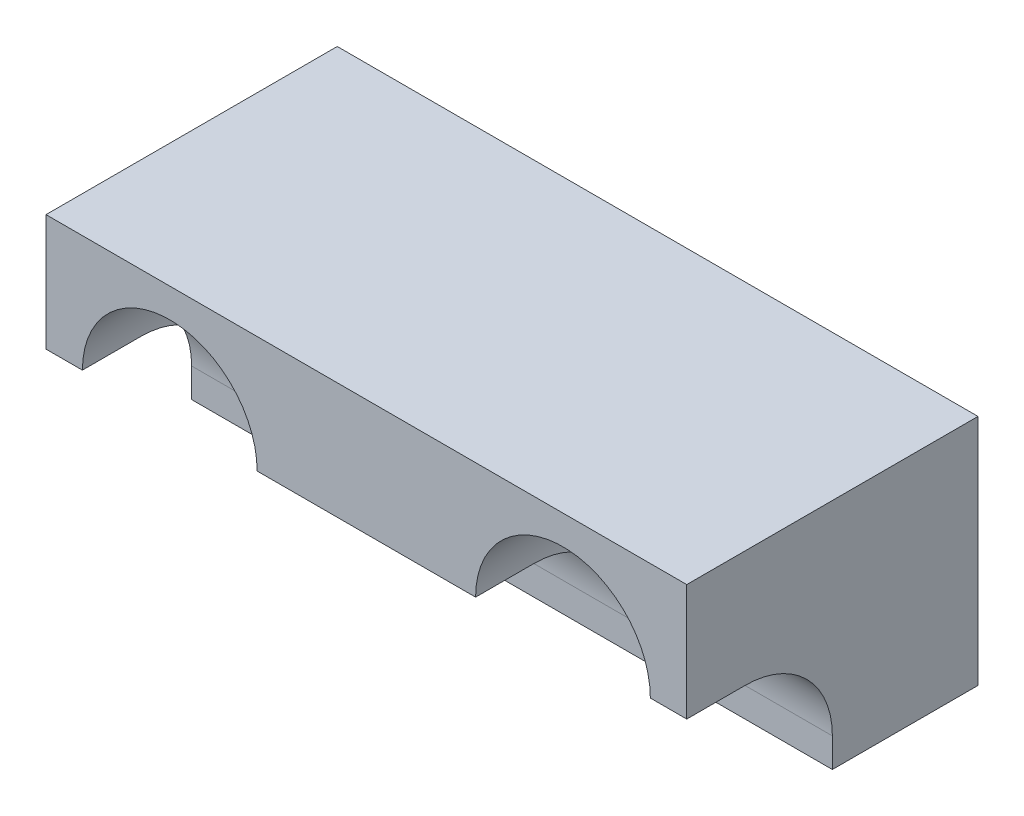
SolidWorks part; units mm, degrees
ref_plane "Front" through (0, 0, 0) normal (0, 0, 1) x (1, 0, 0)
ref_plane "Top" through (0, 0, 0) normal (0, 1, 0) x (1, 0, 0)
ref_plane "Right" through (0, 0, 0) normal (1, 0, 0) x (0, 0, -1)
sketch "Эскиз1" plane through (0, 0, 0) normal (0, 0, 1) x (1, 0, 0)
  line L0 (-6.75, 0) -> (6.75, 0) construction
  line L1 (-11, -4) -> (11, -4)
  line L2 (-11, -4) -> (-11, 4)
  line L3 (-11, 4) -> (11, 4)
  line L4 (11, -4) -> (11, 4)
  line L5 (-11, -4) -> (11, 4) construction
  line L6 (-11, 4) -> (11, -4) construction
  line L7 (0, 4) -> (0, -4) construction
  circle A0 centre (-6.75, 0) radius 1.5
  circle A1 centre (6.75, 0) radius 1.5
  point P0 (0, 0)
  point P12 (0, 0)
  dimension "D1" = 22
  dimension "D2" = 8
  dimension "D5" = 13.5
extrude "Бобышка-Вытянуть1" add sketch "Эскиз1" along normal blind 5
sketch "Эскиз2" plane through (0, 0, 5) normal (0, 0, 1) x (1, 0, 0)
  line L0 (11, -4) -> (11, 4) construction
  line L1 (-11, 4) -> (11, 4)
  line L2 (-11, 4) -> (-11, 0)
  line L3 (-11, 0) -> (11, 0)
  line L4 (11, 4) -> (11, 0)
extrude "Бобышка-Вытянуть2" add sketch "Эскиз2" along normal blind 5
sketch "Эскиз3" plane through (0, 0, 5) normal (0, 0, -1) x (-1, 0, 0)
  line L0 (-5.25, 0) -> (-8.25, 0) construction
  line L1 (8.25, 0) -> (5.25, 0) construction
  circle A0 centre (-6.75, 0) radius 3
  circle A1 centre (6.75, 0) radius 3
extrude "Вырез-Вытянуть1" cut sketch "Эскиз3" against normal blind 5
fillet "Скругление1" radius 3 3 edges at (10.375, 0, 5) (-10.375, 0, 5) (0, 0, 5)
